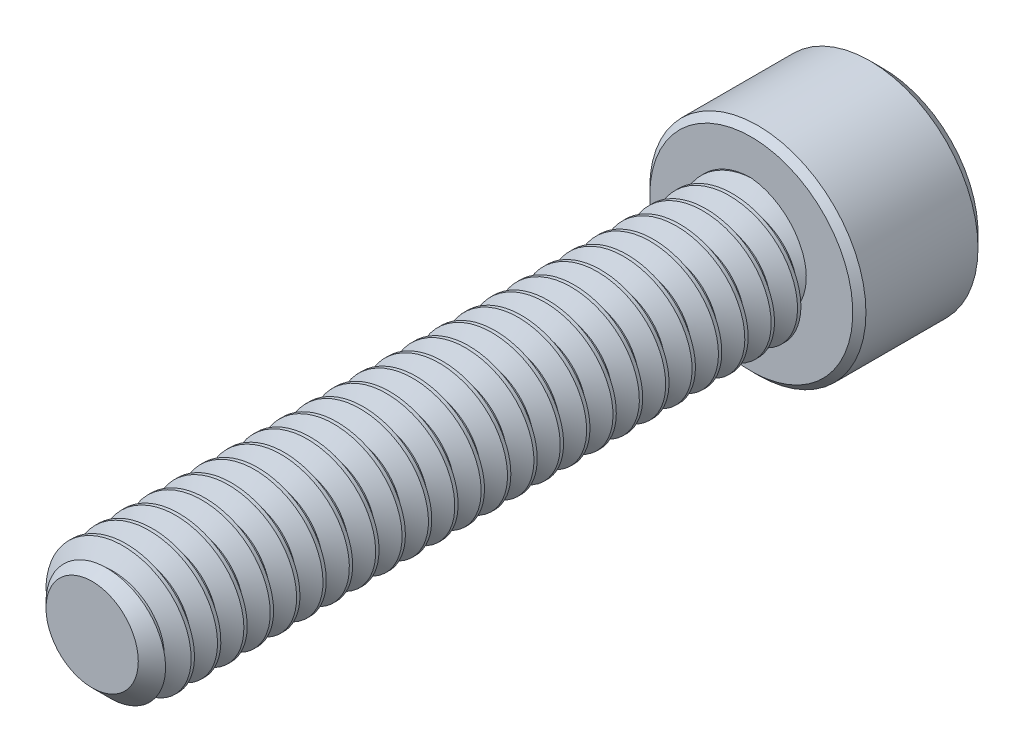
SolidWorks part; units mm, degrees
ref_plane "Front Plane" through (0, 0, 0) normal (0, 0, 1) x (1, 0, 0)
ref_plane "Top Plane" through (0, 0, 0) normal (0, 1, 0) x (1, 0, 0)
ref_plane "Right Plane" through (0, 0, 0) normal (1, 0, 0) x (0, 0, -1)
sketch "Sketch1" plane through (0, 0, 0) normal (0, 0, 1) x (1, 0, 0)
  line L0 (0, 1.5875) -> (0, -1.5875) construction
  circle A0 centre (0, 0) radius 1.5875
  dimension "OD" = 3.175
extrude "Extrude1" add sketch "Sketch1" against normal blind 15.875
sketch "Sketch2" plane through (0, 0, 0) normal (0, 0, 1) x (1, 0, 0)
  circle A0 centre (0, 0) radius 1.5875 construction
  circle A1 centre (0, 0) radius 1.5875
curve "Helix/Spiral1" pitch 0.635 height 16.51 turns 26 parameters "pitch"=0.635
chamfer "Chamfer3" distance 0.4763 angle 45 1 edges at (1.5875, 0, 0)
sketch "Sketch3" plane through (0, 0, 0) normal (1, 0, 0) x (0, 0, -1)
  line L0 (-0.5556, 1.5875) -> (-0.3175, 1.1751)
  line L1 (-0.3175, 1.1751) -> (-0.2381, 1.1751)
  line L2 (-0.2381, 1.1751) -> (0, 1.5875)
  line L3 (-0.5556, 1.5875) -> (0, 1.5875)
  line L4 (-0.2778, 1.5875) -> (-0.2778, 1.1751) construction
  line L5 (-0.4366, 1.3813) -> (-0.1191, 1.3813) construction
  line L6 (0, 1.5875) -> (0, -1.5875) construction
  dimension "D1" = 0.0794
  dimension "D2" = 0.3175
  dimension "D3" = 60
sweep "Cut-Sweep1" cut profiles "Sketch3" path "Helix/Spiral1" align with end faces yes
sketch "Sketch6" plane through (0, 0, -15.875) normal (0, 0, -1) x (-1, 0, 0)
  circle A0 centre (0, 0) radius 2.6035
  dimension "head dia" = 5.207
extrude "Extrude2" add sketch "Sketch6" along normal blind 3.175
sketch "Sketch7" plane through (0, 0, -19.05) normal (0, 0, -1) x (-1, 0, 0)
  line L1 (0, 1.3748) -> (-1.1906, 0.6874)
  line L2 (-1.1906, 0.6874) -> (-1.1906, -0.6874)
  line L3 (-1.1906, -0.6874) -> (0, -1.3748)
  line L4 (0, -1.3748) -> (1.1906, -0.6874)
  line L5 (1.1906, -0.6874) -> (1.1906, 0.6874)
  line L6 (1.1906, 0.6874) -> (0, 1.3748)
  circle A0 centre (0, 0) radius 1.1906 construction
  dimension "hex dia" = 2.3813
extrude "Cut-Extrude1" cut sketch "Sketch7" against normal blind 1.7859
sketch "Sketch8" plane through (0, 0, -19.05) normal (0, 0, -1) x (-1, 0, 0)
  circle A0 centre (0, 0) radius 1.3748
extrude "Cut-Extrude2" cut sketch "Sketch8" against normal blind 0.3175 draft 45
chamfer "Chamfer1" distance 0.3175 angle 45 1 edges at (-2.6035, 0, -19.05)
chamfer "Chamfer2" distance 0.1588 angle 45 1 edges at (-2.6035, 0, -15.875)
sketch "Sketch9" plane through (0, 0, 0) normal (1, 0, 0) x (0, 0, -1)
  line L0 (0, 1.5875) -> (0, -1.5875) construction
  line L1 (3.4925, 1.5875) -> (3.4925, -1.5875) construction
  line L2 (15.875, 2.6035) -> (15.875, -2.6035) construction
  line L3 (19.05, 2.6035) -> (19.05, -2.6035) construction
  line L4 (19.05, 0) -> (0, 0) construction
  dimension "D1" = 3.4925
  dimension "D2" = 3.175
  dimension "D3" = 5.207
  dimension "D4" = 15.875
equation "\"D3@Helix/Spiral1\" = \"screw length@Extrude1\"+\"pitch@Helix/Spiral1\""
equation "\"D1@Sketch3\" = \"pitch@Helix/Spiral1\"*.125"
equation "\"D2@Sketch3\" = \"pitch@Helix/Spiral1\"*.5"
equation "\"D1@Cut-Extrude1\" = \"hex dia@Sketch7\"*.75"
equation "\"D1@Chamfer1\" = \"head depth@Extrude2\"/10"
equation "\"D1@Sketch9\" = \"pitch@Helix/Spiral1\"*5.5"
equation "\"D1@Chamfer2\" = \"D1@Chamfer1\"/2"
equation "\"D1@Cut-Extrude2\" = \"D1@Chamfer2\"*2"
equation "\"D1@Chamfer3\" = \"pitch@Helix/Spiral1\"*.750"
equation "\"D2@Sketch9\" = \"head depth@Extrude2\""
equation "\"D3@Sketch9\" = \"head dia@Sketch6\""
equation "\"D4@Sketch9\" = \"screw length@Extrude1\""
